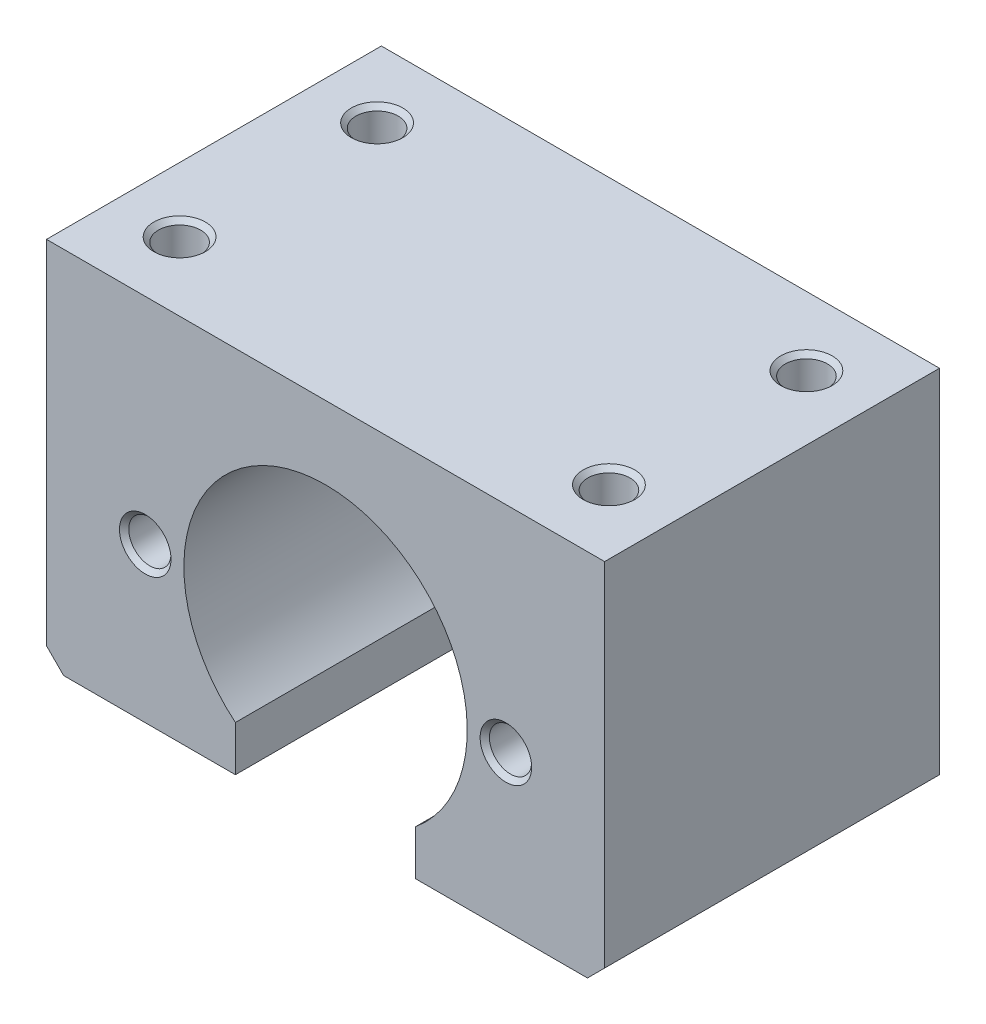
SolidWorks part; units mm, degrees
ref_plane "前视基准面" through (0, 0, 0) normal (0, 0, 1) x (1, 0, 0)
ref_plane "上视基准面" through (0, 0, 0) normal (0, 1, 0) x (1, 0, 0)
ref_plane "右视基准面" through (0, 0, 0) normal (1, 0, 0) x (0, 0, -1)
sketch "草图1" plane through (0, 0, 0) normal (0, 0, 1) x (1, 0, 0)
  line L0 (-32.5, 25) -> (-32.5, -16)
  line L1 (-32.5, -16) -> (-30.5, -18)
  line L2 (-30.5, -18) -> (-10.5, -18)
  line L3 (-10.5, -18) -> (-10.5, -12.7279)
  line L4 (10.5, -12.7279) -> (10.5, -18)
  line L5 (10.5, -18) -> (30.5, -18)
  line L6 (30.5, -18) -> (32.5, -16)
  line L7 (32.5, -16) -> (32.5, 25)
  line L8 (32.5, 25) -> (-32.5, 25)
  arc A0 (-10.5, -12.7279) -> (10.5, -12.7279) centre (0, 0) cw
extrude "凸台-拉伸1" add sketch "草图1" against normal blind 19.5 and the other way blind 19.5
ref_plane "基准面4" through (21, 0, 0) normal (1, 0, 0) x (0, 0, -1)
ref_plane "基准面5" through (-21, 0, 0) normal (1, 0, 0) x (0, 0, -1)
sketch "草图2" plane through (21, 0, 0) normal (1, 0, 0) x (0, 0, -1)
  line L0 (-19.5, 0) -> (-19.5, 3)
  line L1 (-19.5, 3) -> (-18.9585, 2.4585)
  line L2 (-18.9585, 2.4585) -> (-7.5, 2.4585)
  line L3 (-7.5, 2.4585) -> (-6.0806, 0)
  line L4 (-6.0806, 0) -> (-19.5, 0)
  line L5 (-6.0806, 0) -> (-19.5, 0) construction
revolve "切除-旋转1" cut sketch "草图2" angle 360 about L5 reverse direction yes
cosmetic thread "装饰螺纹线1" parameters "D1"=10, "D2"=6
sketch "草图3" plane through (-21, 0, 0) normal (1, 0, 0) x (0, 0, -1)
  line L0 (-19.5, 0) -> (-19.5, 3)
  line L1 (-19.5, 3) -> (-18.9585, 2.4585)
  line L2 (-18.9585, 2.4585) -> (-7.5, 2.4585)
  line L3 (-7.5, 2.4585) -> (-6.0806, 0)
  line L4 (-6.0806, 0) -> (-19.5, 0)
  line L5 (-6.0806, 0) -> (-19.5, 0) construction
revolve "切除-旋转2" cut sketch "草图3" angle 360 about L5 reverse direction yes
cosmetic thread "装饰螺纹线2" parameters "D1"=10, "D2"=6
ref_plane "基准面6" through (25, 0, 0) normal (1, 0, 0) x (0, 0, -1)
sketch "草图4" plane through (25, 0, 0) normal (1, 0, 0) x (0, 0, -1)
  line L0 (-11.5, 25) -> (-8.5, 25)
  line L1 (-8.5, 25) -> (-9.0415, 24.4585)
  line L2 (-9.0415, 24.4585) -> (-9.0415, 11)
  line L3 (-9.0415, 11) -> (-11.5, 9.5806)
  line L4 (-11.5, 9.5806) -> (-11.5, 25)
  line L5 (-11.5, 9.5806) -> (-11.5, 25) construction
revolve "切除-旋转3" cut sketch "草图4" angle 360 about L5 reverse direction yes
cosmetic thread "装饰螺纹线3" parameters "D1"=12, "D2"=6
sketch "草图5" plane through (25, 0, 0) normal (1, 0, 0) x (0, 0, -1)
  line L0 (11.5, 25) -> (14.5, 25)
  line L1 (14.5, 25) -> (13.9585, 24.4585)
  line L2 (13.9585, 24.4585) -> (13.9585, 11)
  line L3 (13.9585, 11) -> (11.5, 9.5806)
  line L4 (11.5, 9.5806) -> (11.5, 25)
  line L5 (11.5, 9.5806) -> (11.5, 25) construction
revolve "切除-旋转4" cut sketch "草图5" angle 360 about L5 reverse direction yes
cosmetic thread "装饰螺纹线4" parameters "D1"=12, "D2"=6
ref_plane "基准面7" through (-25, 0, 0) normal (1, 0, 0) x (0, 0, -1)
sketch "草图6" plane through (-25, 0, 0) normal (1, 0, 0) x (0, 0, -1)
  line L0 (-11.5, 25) -> (-8.5, 25)
  line L1 (-8.5, 25) -> (-9.0415, 24.4585)
  line L2 (-9.0415, 24.4585) -> (-9.0415, 11)
  line L3 (-9.0415, 11) -> (-11.5, 9.5806)
  line L4 (-11.5, 9.5806) -> (-11.5, 25)
  line L5 (-11.5, 9.5806) -> (-11.5, 25) construction
sketch "草图7" plane through (-25, 0, 0) normal (1, 0, 0) x (0, 0, -1)
  line L0 (11.5, 25) -> (14.5, 25)
  line L1 (14.5, 25) -> (13.9585, 24.4585)
  line L2 (13.9585, 24.4585) -> (13.9585, 11)
  line L3 (13.9585, 11) -> (11.5, 9.5806)
  line L4 (11.5, 9.5806) -> (11.5, 25)
  line L5 (11.5, 9.5806) -> (11.5, 25) construction
revolve "切除-旋转5" cut sketch "草图6" angle 360 about L5 reverse direction yes
cosmetic thread "装饰螺纹线5" parameters "D1"=12, "D2"=6
revolve "切除-旋转6" cut sketch "草图7" angle 360 about L5 reverse direction yes
cosmetic thread "装饰螺纹线6" parameters "D1"=12, "D2"=6
ref_plane "基准面8" through (0, 0, 19.5) normal (0, 0, 1) x (1, 0, 0)
ref_plane "kue XY" through (0, 0, 19.5) normal (0, 0, 1) x (1, 0, 0)
ref_plane "kue XZ" through (0, 0, 0) normal (0, -1, 0) x (-1, 0, 0)
ref_plane "kue YZ" through (0, 0, 0) normal (1, 0, 0) x (0, 0, -1)
ref_axis "kue X" through (-80.9, 0, 19.5) along (1, 0, 0)
ref_axis "kue Y" through (0, -50, 19.5) along (0, 1, 0)
ref_axis "kue Z" through (0, 0, 80.9) along (0, 0, -1)
sketch3d "kue"
  point P0 (0, 0, 19.5)
